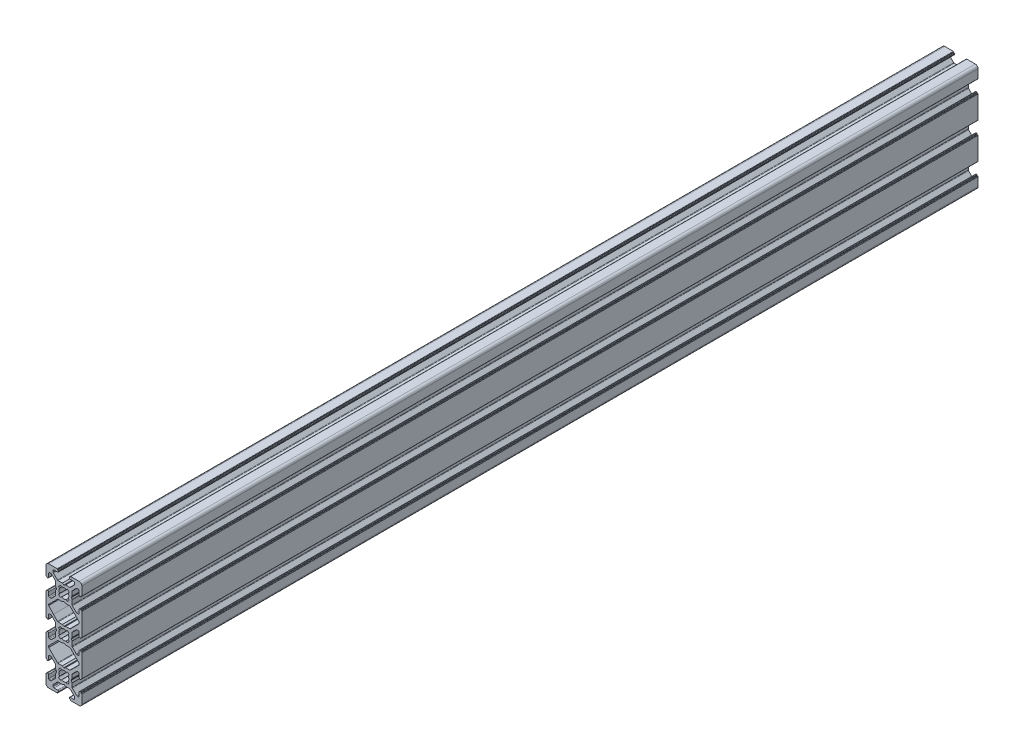
SolidWorks part; units mm, degrees
material "6061 Alloy"
ref_plane "Front Plane" through (0, 0, 0) normal (0, 0, 1) x (1, 0, 0)
ref_plane "Top Plane" through (0, 0, 0) normal (0, 1, 0) x (1, 0, 0)
ref_plane "Right Plane" through (0, 0, 0) normal (1, 0, 0) x (0, 0, -1)
sketch "Sketch2" plane through (0, 0, 0) normal (0, 0, 1) x (1, 0, 0)
  line L0 (0, -19.2121) -> (0, 56.5718) construction
  line L1 (8.5, 16.4558) -> (8.5, 14.5058)
  line L2 (10, 36.2558) -> (10, 23.6558)
  line L3 (-8.5, 30.4451) -> (-8.5, 29.884)
  line L4 (8.5, 30.4451) -> (8.5, 29.5607)
  line L5 (-3.5858, 4.6464) -> (-8.5, 9.5607)
  line L6 (-4.7214, 3.4608) -> (-7.1142, 5.8536)
  line L7 (-3.75, -10) -> (-8.5, -10)
  line L8 (-4.7214, -3.4608) -> (-7.1142, -5.8536)
  line L9 (-9.7, -3.55) -> (-9.8, -3.55)
  line L10 (-9.5, -3.2) -> (-9.5, -3.35)
  line L11 (-7.4678, -6) -> (-8, -6)
  line L12 (-9, -3) -> (-9.3, -3)
  line L13 (-8.5, -3.5) -> (-8.5, -5.5)
  line L14 (-10, -3.75) -> (-10, -8.5)
  line L15 (-7.4678, 6) -> (-8, 6)
  line L16 (-9.7, 3.55) -> (-9.8, 3.55)
  line L17 (-9.5, 3.2) -> (-9.5, 3.35)
  line L18 (-9, 3) -> (-9.3, 3)
  line L19 (-8.5, 3.5) -> (-8.5, 5.5)
  line L20 (-10, 16.2558) -> (-10, 3.75)
  line L21 (-4.575, -3.1072) -> (-4.575, -1.0835)
  line L22 (4.575, -3.1072) -> (4.575, -1.0835)
  line L23 (3.2322, -4.5) -> (0.9536, -4.5)
  line L24 (-3.2322, -4.5) -> (-0.9536, -4.5)
  line L25 (-0.8536, -4.4732) -> (-0.1, -4.0381)
  line L26 (0.8536, -4.4732) -> (0.1, -4.0381)
  line L27 (-3.5, -8.5) -> (-5.5, -8.5)
  line L28 (-3.2, -9.5) -> (-3.35, -9.5)
  line L29 (-3.55, -9.7) -> (-3.55, -9.8)
  line L30 (-6, -7.2678) -> (-6, -8)
  line L31 (-3.5858, -4.6464) -> (-5.8536, -6.9142)
  line L32 (-3, -9) -> (-3, -9.3)
  line L33 (3.55, -9.7) -> (3.55, -9.8)
  line L34 (3.2, -9.5) -> (3.35, -9.5)
  line L35 (6, -7.2678) -> (6, -8)
  line L36 (3, -9) -> (3, -9.3)
  line L37 (3.5, -8.5) -> (5.5, -8.5)
  line L38 (3.75, -10) -> (8.5, -10)
  line L39 (10, -3.7) -> (10, -8.5)
  line L40 (8.5, -3.5) -> (8.5, -5.5)
  line L41 (9.5, -3.2) -> (9.5, -3.3)
  line L42 (9.7, -3.5) -> (9.8, -3.5)
  line L43 (7.4678, -6) -> (8, -6)
  line L44 (4.7214, -3.4608) -> (7.1142, -5.8536)
  line L45 (3.5858, -4.6464) -> (5.8536, -6.9142)
  line L46 (9, -3) -> (9.3, -3)
  line L47 (3.5858, 4.6464) -> (8.5, 9.5607)
  line L48 (3.2322, 4.5) -> (0.9536, 4.5)
  line L49 (-3.2322, 4.5) -> (-0.9536, 4.5)
  line L50 (-0.8536, 4.4732) -> (-0.1, 4.0381)
  line L51 (0.8536, 4.4732) -> (0.1, 4.0381)
  line L52 (1.2582, 2.4453) -> (1.9099, 2.9922)
  line L53 (-4.575, 3.1072) -> (-4.575, 1.0835)
  line L54 (-4.5482, 0.9835) -> (-4.0381, 0.1)
  line L55 (-4.5482, -0.9835) -> (-4.0381, -0.1)
  line L56 (-1.2623, 2.4431) -> (-1.9139, 2.9896)
  line L57 (-2.4453, 1.2582) -> (-2.9922, 1.9099)
  line L58 (-2.4431, -1.2623) -> (-2.9897, -1.9139)
  line L59 (-1.2582, -2.4453) -> (-1.9099, -2.9922)
  line L60 (1.2623, -2.4431) -> (1.9139, -2.9897)
  line L61 (2.4453, 1.2582) -> (2.9896, 1.9139)
  line L62 (4.5482, -0.9835) -> (4.0381, -0.1)
  line L63 (4.5482, 0.9835) -> (4.0381, 0.1)
  line L64 (4.575, 3.1072) -> (4.575, 1.0835)
  line L65 (2.4453, -1.2582) -> (2.9922, -1.9099)
  line L66 (9.7, 3.5) -> (9.8, 3.5)
  line L67 (9.5, 3.2) -> (9.5, 3.3)
  line L68 (7.4678, 6) -> (8, 6)
  line L69 (9, 3) -> (9.3, 3)
  line L70 (8.5, 3.5) -> (8.5, 5.5)
  line L71 (10, 3.7) -> (10, 16.2558)
  line L72 (4.7214, 3.4608) -> (7.1142, 5.8536)
  line L73 (-4.7214, 36.345) -> (-6.9142, 34.1522)
  line L74 (-3.5858, 35.3593) -> (-8.5, 30.4451)
  line L75 (-4.7214, 43.6666) -> (-6.9142, 45.8593)
  line L76 (-3.75, 50) -> (-8.5, 50)
  line L77 (-10, 43.6558) -> (-10, 48.5)
  line L78 (-8.5, 43.4558) -> (-8.5, 45.5058)
  line L79 (0, 40.0058) -> (15.2221, 40.0058) construction
  line L80 (-8.5, 36.4558) -> (-8.5, 34.5058)
  line L81 (-9, 36.9558) -> (-9.3, 36.9558)
  line L82 (-7.2678, 34.0058) -> (-8, 34.0058)
  line L83 (-9.5, 36.7558) -> (-9.5, 36.6558)
  line L84 (-9.7, 36.4558) -> (-9.8, 36.4558)
  line L85 (-9, 42.9558) -> (-9.3, 42.9558)
  line L86 (-9.5, 43.1558) -> (-9.5, 43.2558)
  line L87 (-9.7, 43.4558) -> (-9.8, 43.4558)
  line L88 (-7.2678, 46.0058) -> (-8, 46.0058)
  line L89 (4.7214, 43.6666) -> (6.9142, 45.8593)
  line L90 (10, 43.6558) -> (10, 48.5)
  line L91 (8.5, 43.4558) -> (8.5, 45.5058)
  line L92 (3.5858, 35.3593) -> (8.5, 30.4451)
  line L93 (-4.7214, 16.345) -> (-6.9142, 14.1522)
  line L94 (3.2322, 35.5058) -> (0.9536, 35.5058)
  line L95 (1.2582, 37.5605) -> (1.8871, 37.0581)
  line L96 (-1.2582, 37.5605) -> (-1.8871, 37.0581)
  line L97 (-2.4453, 38.7476) -> (-2.9477, 38.1187)
  line L98 (-2.4453, 41.264) -> (-2.9477, 41.8928)
  line L99 (-1.2582, 42.4511) -> (-1.8871, 42.9535)
  line L100 (0.8536, 35.5326) -> (0.1, 35.9677)
  line L101 (-0.8536, 35.5326) -> (-0.1, 35.9677)
  line L102 (-3.2322, 35.5058) -> (-0.9536, 35.5058)
  line L103 (-4.575, 36.6986) -> (-4.575, 39.1772)
  line L104 (-4.5482, 39.2772) -> (-4.142, 39.9808)
  line L105 (-4.5482, 40.8844) -> (-4.142, 40.1808)
  line L106 (-4.575, 43.313) -> (-4.575, 40.9844)
  line L107 (1.2582, 42.4511) -> (1.8871, 42.9535)
  line L108 (9, 42.9558) -> (9.3, 42.9558)
  line L109 (9.5, 43.1558) -> (9.5, 43.2558)
  line L110 (9.7, 43.4558) -> (9.8, 43.4558)
  line L111 (9, 36.9558) -> (9.3, 36.9558)
  line L112 (4.7214, 36.345) -> (6.9142, 34.1522)
  line L113 (7.2678, 34.0058) -> (8, 34.0058)
  line L114 (9.7, 36.4558) -> (9.8, 36.4558)
  line L115 (9.5, 36.7558) -> (9.5, 36.6558)
  line L116 (8.5, 36.4558) -> (8.5, 34.5058)
  line L117 (2.4453, 38.7476) -> (2.9477, 38.1187)
  line L118 (4.575, 43.313) -> (4.575, 40.9844)
  line L119 (4.5482, 40.8844) -> (4.142, 40.1808)
  line L120 (4.5482, 39.2772) -> (4.142, 39.9808)
  line L121 (4.575, 36.6986) -> (4.575, 39.1772)
  line L122 (2.4453, 41.264) -> (2.9477, 41.8928)
  line L123 (3.2322, 44.5) -> (0.9536, 44.5)
  line L124 (-3.55, 49.7) -> (-3.55, 49.8)
  line L125 (-3.2, 49.5) -> (-3.35, 49.5)
  line L126 (-3.5858, 44.6464) -> (-5.8536, 46.9142)
  line L127 (-6, 47.2678) -> (-6, 48)
  line L128 (0.8536, 44.4732) -> (0.0592, 44.0146)
  line L129 (-0.8536, 44.4732) -> (-0.0592, 44.0146)
  line L130 (-3.2322, 44.5) -> (-0.9536, 44.5)
  line L131 (-3, 49) -> (-3, 49.3)
  line L132 (-3.5, 48.5) -> (-5.5, 48.5)
  line L133 (3, 49) -> (3, 49.3)
  line L134 (3.5858, 44.6464) -> (5.8536, 46.9142)
  line L135 (6, 47.2678) -> (6, 48)
  line L136 (3.55, 49.7) -> (3.55, 49.8)
  line L137 (3.2, 49.5) -> (3.35, 49.5)
  line L138 (3.5, 48.5) -> (5.5, 48.5)
  line L139 (3.75, 50) -> (8.5, 50)
  line L140 (-34.2612, 0) -> (36.5039, 0) construction
  line L141 (-3.5858, 15.3593) -> (-8.5, 10.4451)
  line L142 (-4.7214, 23.6666) -> (-6.9142, 25.8593)
  line L143 (-8.5, 10.4451) -> (-8.5, 9.5607)
  line L144 (-9.5, 16.7558) -> (-9.5, 16.6558)
  line L145 (-9.7, 16.4558) -> (-9.8, 16.4558)
  line L146 (-9, 16.9558) -> (-9.3, 16.9558)
  line L147 (-7.2678, 14.0058) -> (-8, 14.0058)
  line L148 (-5.8536, 26.9142) -> (-8.5, 29.884)
  line L149 (-8.5, 16.4558) -> (-8.5, 14.5058)
  line L150 (-9.8, 23.4558) -> (-9.7, 23.4558)
  line L151 (-9, 22.9558) -> (-9.3, 22.9558)
  line L152 (-9.5, 23.1558) -> (-9.5, 23.2558)
  line L153 (-7.2678, 26.0058) -> (-8, 26.0058)
  line L154 (7.2678, 26.0058) -> (8, 26.0058)
  line L155 (4.7214, 23.6666) -> (6.9142, 25.8593)
  line L156 (-10, 36.2558) -> (-10, 23.6558)
  line L157 (8.5, 25.5058) -> (8.5, 23.4558)
  line L158 (3.5858, 15.3593) -> (8.5, 10.4451)
  line L159 (3.2322, 15.5058) -> (0.9536, 15.5058)
  line L160 (1.2582, 17.5605) -> (1.8871, 17.0581)
  line L161 (-1.2582, 17.5605) -> (-1.8871, 17.0581)
  line L162 (-2.4453, 18.7476) -> (-2.9477, 18.1187)
  line L163 (-2.4453, 21.264) -> (-2.9477, 21.8928)
  line L164 (-1.2582, 22.4511) -> (-1.8871, 22.9535)
  line L165 (0.8536, 15.5326) -> (0.1, 15.9677)
  line L166 (-0.8536, 15.5326) -> (-0.1, 15.9677)
  line L167 (-3.2322, 15.5058) -> (-0.9536, 15.5058)
  line L168 (-4.575, 16.6986) -> (-4.575, 19.1772)
  line L169 (-4.5482, 19.2772) -> (-4.142, 19.9808)
  line L170 (-4.5482, 20.8844) -> (-4.142, 20.1808)
  line L171 (-4.575, 23.313) -> (-4.575, 20.9844)
  line L172 (1.2582, 22.4511) -> (1.8871, 22.9535)
  line L173 (9, 22.9558) -> (9.3, 22.9558)
  line L174 (9.5, 23.1558) -> (9.5, 23.2558)
  line L175 (9.8, 23.4558) -> (9.7, 23.4558)
  line L176 (9, 16.9558) -> (9.3, 16.9558)
  line L177 (4.7214, 16.345) -> (6.9142, 14.1522)
  line L178 (7.2678, 14.0058) -> (8, 14.0058)
  line L179 (9.7, 16.4558) -> (9.8, 16.4558)
  line L180 (9.5, 16.7558) -> (9.5, 16.6558)
  line L181 (5.8536, 26.9142) -> (8.5, 29.5607)
  line L182 (2.4453, 18.7476) -> (2.9477, 18.1187)
  line L183 (4.575, 23.313) -> (4.575, 20.9844)
  line L184 (4.5482, 20.8844) -> (4.142, 20.1808)
  line L185 (4.5482, 19.2772) -> (4.142, 19.9808)
  line L186 (4.575, 16.6986) -> (4.575, 19.1772)
  line L187 (2.4453, 21.264) -> (2.9477, 21.8928)
  line L188 (3.2322, 24.5) -> (0.9536, 24.5)
  line L191 (-3.5858, 24.6464) -> (-5.8536, 26.9142)
  line L192 (-8.5, 25.5058) -> (-8.5, 23.4558)
  line L193 (0.8536, 24.4732) -> (0.0592, 24.0146)
  line L194 (-0.8536, 24.4732) -> (-0.0592, 24.0146)
  line L195 (-3.2322, 24.5) -> (-0.9536, 24.5)
  line L196 (8.5, 10.4451) -> (8.5, 9.5607)
  line L199 (3.5858, 24.6464) -> (5.8536, 26.9142)
  line L206 (0, 20.0058) -> (15.2221, 20.0058) construction
  line L279 (7.2678, 46.0058) -> (8, 46.0058)
  line L280 (-3.75, 30) -> (-8.5, 30) [skipped]
  line L281 (-3.55, 29.7) -> (-3.55, 29.8) [skipped]
  line L282 (-3.2, 29.5) -> (-3.35, 29.5) [skipped]
  line L283 (-3, 29) -> (-3, 29.3) [skipped]
  line L284 (-3.5, 28.5) -> (-5.5, 28.5) [skipped]
  line L285 (-6, 27.2678) -> (-6, 28) [skipped]
  line L286 (3.5, 28.5) -> (5.5, 28.5) [skipped]
  line L287 (3, 29) -> (3, 29.3) [skipped]
  line L288 (3.75, 30) -> (8.5, 30) [skipped]
  line L289 (3.55, 29.7) -> (3.55, 29.8) [skipped]
  line L290 (3.2, 29.5) -> (3.35, 29.5) [skipped]
  line L291 (6, 27.2678) -> (6, 28) [skipped]
  line L292 (10, 23.6558) -> (10, 28.5) [skipped]
  line L293 (8.5, 16.4558) -> (8.5, 14.5058) [skipped]
  line L294 (-7.2678, 14.0058) -> (-8, 14.0058) [skipped]
  line L295 (-10, 23.6558) -> (-10, 28.5) [skipped]
  line L296 (-9.7, 23.4558) -> (-9.8, 23.4558) [skipped]
  line L297 (-7.2678, 26.0058) -> (-8, 26.0058) [skipped]
  line L298 (-8.5, 23.4558) -> (-8.5, 25.5058) [skipped]
  line L299 (-8.5, 16.4558) -> (-8.5, 14.5058) [skipped]
  line L300 (-9, 16.9558) -> (-9.3, 16.9558) [skipped]
  line L301 (-9.5, 16.7558) -> (-9.5, 16.6558) [skipped]
  line L302 (-9.7, 16.4558) -> (-9.8, 16.4558) [skipped]
  line L303 (9, 22.9558) -> (9.3, 22.9558) [skipped]
  line L304 (9.5, 23.1558) -> (9.5, 23.2558) [skipped]
  line L305 (9.7, 23.4558) -> (9.8, 23.4558) [skipped]
  line L306 (7.2678, 26.0058) -> (8, 26.0058) [skipped]
  line L307 (8.5, 23.4558) -> (8.5, 25.5058) [skipped]
  arc A0 (-5.8536, -6.9142) -> (-6, -7.2678) centre (-5.5, -7.2678) ccw
  arc A1 (-6, -8) -> (-5.5, -8.5) centre (-5.5, -8) ccw
  arc A2 (-8.5, -3.5) -> (-9, -3) centre (-9, -3.5) ccw
  arc A3 (-9.7, -3.55) -> (-9.5, -3.35) centre (-9.7, -3.35) ccw
  arc A4 (-9.8, -3.55) -> (-10, -3.75) centre (-9.8, -3.75) ccw
  arc A5 (-9.3, -3) -> (-9.5, -3.2) centre (-9.3, -3.2) ccw
  arc A6 (-7.4678, -6) -> (-7.1142, -5.8536) centre (-7.4678, -5.5) ccw
  arc A7 (-10, -8.5) -> (-8.5, -10) centre (-8.5, -8.5) ccw
  arc A8 (-8.5, -5.5) -> (-8, -6) centre (-8, -5.5) ccw
  arc A9 (-8, 6) -> (-8.5, 5.5) centre (-8, 5.5) ccw
  arc A10 (-7.1142, 5.8536) -> (-7.4678, 6) centre (-7.4678, 5.5) ccw
  arc A11 (-9.5, 3.35) -> (-9.7, 3.55) centre (-9.7, 3.35) ccw
  arc A12 (-10, 3.75) -> (-9.8, 3.55) centre (-9.8, 3.75) ccw
  arc A13 (-9.5, 3.2) -> (-9.3, 3) centre (-9.3, 3.2) ccw
  arc A14 (-9, 3) -> (-8.5, 3.5) centre (-9, 3.5) ccw
  arc A15 (9, -3) -> (8.5, -3.5) centre (9, -3.5) ccw
  arc A16 (-4.7214, -3.4608) -> (-4.575, -3.1072) centre (-5.075, -3.1072) ccw
  arc A17 (-3.2322, -4.5) -> (-3.5858, -4.6464) centre (-3.2322, -5) ccw
  arc A18 (0.8536, -4.4732) -> (0.9536, -4.5) centre (0.9536, -4.3) ccw
  arc A19 (-0.9536, -4.5) -> (-0.8536, -4.4732) centre (-0.9536, -4.3) ccw
  arc A20 (0.1, -4.0381) -> (-0.1, -4.0381) centre (0, -4.2113) ccw
  arc A21 (-3.2, -9.5) -> (-3, -9.3) centre (-3.2, -9.3) ccw
  arc A22 (-3.75, -10) -> (-3.55, -9.8) centre (-3.75, -9.8) ccw
  arc A23 (-3.35, -9.5) -> (-3.55, -9.7) centre (-3.35, -9.7) ccw
  arc A24 (-3, -9) -> (-3.5, -8.5) centre (-3.5, -9) ccw
  arc A25 (3.5858, -4.6464) -> (3.2322, -4.5) centre (3.2322, -5) ccw
  arc A26 (4.575, -3.1072) -> (4.7214, -3.4608) centre (5.075, -3.1072) ccw
  arc A27 (3.55, -9.7) -> (3.35, -9.5) centre (3.35, -9.7) ccw
  arc A28 (3.55, -9.8) -> (3.75, -10) centre (3.75, -9.8) ccw
  arc A29 (3, -9.3) -> (3.2, -9.5) centre (3.2, -9.3) ccw
  arc A30 (6, -7.2678) -> (5.8536, -6.9142) centre (5.5, -7.2678) ccw
  arc A31 (8.5, -10) -> (10, -8.5) centre (8.5, -8.5) ccw
  arc A32 (5.5, -8.5) -> (6, -8) centre (5.5, -8) ccw
  arc A33 (9.5, -3.2) -> (9.3, -3) centre (9.3, -3.2) ccw
  arc A34 (10, -3.7) -> (9.8, -3.5) centre (9.8, -3.7) ccw
  arc A35 (9.5, -3.3) -> (9.7, -3.5) centre (9.7, -3.3) ccw
  arc A36 (7.1142, -5.8536) -> (7.4678, -6) centre (7.4678, -5.5) ccw
  arc A37 (8, -6) -> (8.5, -5.5) centre (8, -5.5) ccw
  arc A38 (3.5, -8.5) -> (3, -9) centre (3.5, -9) ccw
  arc A39 (2.9896, 1.9139) -> (1.9099, 2.9922) centre (0, 0) ccw
  arc A40 (1.9139, -2.9897) -> (2.9922, -1.9099) centre (0, 0) ccw
  arc A41 (1.2582, 2.4453) -> (-1.2623, 2.4431) centre (0, 0) ccw
  arc A42 (-0.1, 4.0381) -> (0.1, 4.0381) centre (0, 4.2113) ccw
  arc A43 (0.9536, 4.5) -> (0.8536, 4.4732) centre (0.9536, 4.3) ccw
  arc A44 (-0.8536, 4.4732) -> (-0.9536, 4.5) centre (-0.9536, 4.3) ccw
  arc A45 (-3.5858, 4.6464) -> (-3.2322, 4.5) centre (-3.2322, 5) ccw
  arc A46 (-4.575, 3.1072) -> (-4.7214, 3.4608) centre (-5.075, 3.1072) ccw
  arc A47 (-4.5482, -0.9835) -> (-4.575, -1.0835) centre (-4.375, -1.0835) ccw
  arc A48 (-4.575, 1.0835) -> (-4.5482, 0.9835) centre (-4.375, 1.0835) ccw
  arc A49 (-4.0381, -0.1) -> (-4.0381, 0.1) centre (-4.2113, 0) ccw
  arc A50 (-1.9139, 2.9896) -> (-2.9922, 1.9099) centre (0, 0) ccw
  arc A51 (-2.9897, -1.9139) -> (-1.9099, -2.9922) centre (0, 0) ccw
  arc A52 (-2.4453, 1.2582) -> (-2.4431, -1.2623) centre (0, 0) ccw
  arc A53 (-1.2582, -2.4453) -> (1.2623, -2.4431) centre (0, 0) ccw
  arc A54 (3.2322, 4.5) -> (3.5858, 4.6464) centre (3.2322, 5) ccw
  arc A55 (4.7214, 3.4608) -> (4.575, 3.1072) centre (5.075, 3.1072) ccw
  arc A56 (4.5482, 0.9835) -> (4.575, 1.0835) centre (4.375, 1.0835) ccw
  arc A57 (4.575, -1.0835) -> (4.5482, -0.9835) centre (4.375, -1.0835) ccw
  arc A58 (4.0381, 0.1) -> (4.0381, -0.1) centre (4.2113, 0) ccw
  arc A59 (2.4453, -1.2582) -> (2.4453, 1.2582) centre (0, 0) ccw
  arc A60 (9.7, 3.5) -> (9.5, 3.3) centre (9.7, 3.3) ccw
  arc A61 (9.8, 3.5) -> (10, 3.7) centre (9.8, 3.7) ccw
  arc A62 (9.3, 3) -> (9.5, 3.2) centre (9.3, 3.2) ccw
  arc A63 (7.4678, 6) -> (7.1142, 5.8536) centre (7.4678, 5.5) ccw
  arc A64 (8.5, 5.5) -> (8, 6) centre (8, 5.5) ccw
  arc A65 (8.5, 3.5) -> (9, 3) centre (9, 3.5) ccw
  arc A66 (-6, 47.2678) -> (-5.8536, 46.9142) centre (-5.5, 47.2678) ccw
  arc A67 (-5.5, 48.5) -> (-6, 48) centre (-5.5, 48) ccw
  arc A68 (-9, 42.9558) -> (-8.5, 43.4558) centre (-9, 43.4558) ccw
  arc A69 (-8.5, 36.4558) -> (-9, 36.9558) centre (-9, 36.4558) ccw
  arc A70 (-8.5, 34.5058) -> (-8, 34.0058) centre (-8, 34.5058) ccw
  arc A71 (-7.2678, 34.0058) -> (-6.9142, 34.1522) centre (-7.2678, 34.5058) ccw
  arc A72 (-9.3, 36.9558) -> (-9.5, 36.7558) centre (-9.3, 36.7558) ccw
  arc A73 (-9.8, 36.4558) -> (-10, 36.2558) centre (-9.8, 36.2558) ccw
  arc A74 (-9.7, 36.4558) -> (-9.5, 36.6558) centre (-9.7, 36.6558) ccw
  arc A75 (-9.5, 43.1558) -> (-9.3, 42.9558) centre (-9.3, 43.1558) ccw
  arc A76 (-10, 43.6558) -> (-9.8, 43.4558) centre (-9.8, 43.6558) ccw
  arc A77 (-9.5, 43.2558) -> (-9.7, 43.4558) centre (-9.7, 43.2558) ccw
  arc A78 (-6.9142, 45.8593) -> (-7.2678, 46.0058) centre (-7.2678, 45.5058) ccw
  arc A79 (-8, 46.0058) -> (-8.5, 45.5058) centre (-8, 45.5058) ccw
  arc A80 (-8.5, 50) -> (-10, 48.5) centre (-8.5, 48.5) ccw
  arc A81 (1.8871, 37.0581) -> (2.9477, 38.1187) centre (0, 40.0058) ccw
  arc A82 (2.9477, 41.8928) -> (1.8871, 42.9535) centre (0, 40.0058) ccw
  arc A83 (-1.2582, 37.5605) -> (1.2582, 37.5605) centre (0, 40.0058) ccw
  arc A84 (-2.4453, 41.264) -> (-2.4453, 38.7476) centre (0, 40.0058) ccw
  arc A85 (-2.9477, 38.1187) -> (-1.8871, 37.0581) centre (0, 40.0058) ccw
  arc A86 (-1.8871, 42.9535) -> (-2.9477, 41.8928) centre (0, 40.0058) ccw
  arc A87 (0.1, 35.9677) -> (-0.1, 35.9677) centre (0, 35.7945) ccw
  arc A88 (-0.9536, 35.5058) -> (-0.8536, 35.5326) centre (-0.9536, 35.7058) ccw
  arc A89 (0.8536, 35.5326) -> (0.9536, 35.5058) centre (0.9536, 35.7058) ccw
  arc A90 (-3.2322, 35.5058) -> (-3.5858, 35.3593) centre (-3.2322, 35.0058) ccw
  arc A91 (-4.142, 39.9808) -> (-4.142, 40.1808) centre (-4.3152, 40.0808) ccw
  arc A92 (-4.575, 40.9844) -> (-4.5482, 40.8844) centre (-4.375, 40.9844) ccw
  arc A93 (-4.5482, 39.2772) -> (-4.575, 39.1772) centre (-4.375, 39.1772) ccw
  arc A94 (-4.575, 43.313) -> (-4.7214, 43.6666) centre (-5.075, 43.313) ccw
  arc A95 (-4.7214, 36.345) -> (-4.575, 36.6986) centre (-5.075, 36.6986) ccw
  arc A96 (1.2582, 42.4511) -> (-1.2582, 42.4511) centre (0, 40.0058) ccw
  arc A97 (9, 36.9558) -> (8.5, 36.4558) centre (9, 36.4558) ccw
  arc A98 (8.5, 43.4558) -> (9, 42.9558) centre (9, 43.4558) ccw
  arc A99 (9.3, 42.9558) -> (9.5, 43.1558) centre (9.3, 43.1558) ccw
  arc A100 (9.8, 43.4558) -> (10, 43.6558) centre (9.8, 43.6558) ccw
  arc A101 (9.7, 43.4558) -> (9.5, 43.2558) centre (9.7, 43.2558) ccw
  arc A102 (8, 34.0058) -> (8.5, 34.5058) centre (8, 34.5058) ccw
  arc A103 (6.9142, 34.1522) -> (7.2678, 34.0058) centre (7.2678, 34.5058) ccw
  arc A104 (9.5, 36.6558) -> (9.7, 36.4558) centre (9.7, 36.6558) ccw
  arc A105 (10, 36.2558) -> (9.8, 36.4558) centre (9.8, 36.2558) ccw
  arc A106 (9.5, 36.7558) -> (9.3, 36.9558) centre (9.3, 36.7558) ccw
  arc A107 (2.4453, 38.7476) -> (2.4453, 41.264) centre (0, 40.0058) ccw
  arc A108 (4.142, 40.1808) -> (4.142, 39.9808) centre (4.3152, 40.0808) ccw
  arc A109 (4.575, 39.1772) -> (4.5482, 39.2772) centre (4.375, 39.1772) ccw
  arc A110 (4.5482, 40.8844) -> (4.575, 40.9844) centre (4.375, 40.9844) ccw
  arc A111 (4.575, 36.6986) -> (4.7214, 36.345) centre (5.075, 36.6986) ccw
  arc A112 (4.7214, 43.6666) -> (4.575, 43.313) centre (5.075, 43.313) ccw
  arc A113 (3.5858, 35.3593) -> (3.2322, 35.5058) centre (3.2322, 35.0058) ccw
  arc A114 (-3.5, 48.5) -> (-3, 49) centre (-3.5, 49) ccw
  arc A115 (-3.55, 49.7) -> (-3.35, 49.5) centre (-3.35, 49.7) ccw
  arc A116 (-3.55, 49.8) -> (-3.75, 50) centre (-3.75, 49.8) ccw
  arc A117 (-3, 49.3) -> (-3.2, 49.5) centre (-3.2, 49.3) ccw
  arc A118 (-3.5858, 44.6464) -> (-3.2322, 44.5) centre (-3.2322, 45) ccw
  arc A119 (-0.8536, 44.4732) -> (-0.9536, 44.5) centre (-0.9536, 44.3) ccw
  arc A120 (0.9536, 44.5) -> (0.8536, 44.4732) centre (0.9536, 44.3) ccw
  arc A121 (-0.0592, 44.0146) -> (0.0592, 44.0146) centre (0, 44.1171) ccw
  arc A122 (3, 49) -> (3.5, 48.5) centre (3.5, 49) ccw
  arc A123 (6, 48) -> (5.5, 48.5) centre (5.5, 48) ccw
  arc A124 (5.8536, 46.9142) -> (6, 47.2678) centre (5.5, 47.2678) ccw
  arc A125 (3.35, 49.5) -> (3.55, 49.7) centre (3.35, 49.7) ccw
  arc A126 (3.75, 50) -> (3.55, 49.8) centre (3.75, 49.8) ccw
  arc A127 (3.2, 49.5) -> (3, 49.3) centre (3.2, 49.3) ccw
  arc A128 (8.5, 45.5058) -> (8, 46.0058) centre (8, 45.5058) ccw
  arc A129 (10, 48.5) -> (8.5, 50) centre (8.5, 48.5) ccw
  arc A130 (7.2678, 46.0058) -> (6.9142, 45.8593) centre (7.2678, 45.5058) ccw
  arc A131 (3.2322, 44.5) -> (3.5858, 44.6464) centre (3.2322, 45) ccw
  arc A132 (-7.2678, 26.0058) -> (-6.9142, 25.8593) centre (-7.2678, 25.5058) cw
  arc A133 (-9.5, 16.7558) -> (-9.3, 16.9558) centre (-9.3, 16.7558) cw
  arc A134 (-9, 22.9558) -> (-8.5, 23.4558) centre (-9, 23.4558) ccw
  arc A135 (-10, 16.2558) -> (-9.8, 16.4558) centre (-9.8, 16.2558) cw
  arc A136 (-9.5, 16.6558) -> (-9.7, 16.4558) centre (-9.7, 16.6558) cw
  arc A137 (-7.2678, 14.0058) -> (-6.9142, 14.1522) centre (-7.2678, 14.5058) ccw
  arc A138 (-9, 16.9558) -> (-8.5, 16.4558) centre (-9, 16.4558) cw
  arc A139 (-8, 14.0058) -> (-8.5, 14.5058) centre (-8, 14.5058) cw
  arc A140 (8, 26.0058) -> (8.5, 25.5058) centre (8, 25.5058) cw
  arc A141 (-9.5, 23.1558) -> (-9.3, 22.9558) centre (-9.3, 23.1558) ccw
  arc A142 (-10, 23.6558) -> (-9.8, 23.4558) centre (-9.8, 23.6558) ccw
  arc A143 (-9.5, 23.2558) -> (-9.7, 23.4558) centre (-9.7, 23.2558) ccw
  arc A144 (9, 22.9558) -> (8.5, 23.4558) centre (9, 23.4558) cw
  arc A145 (-8, 26.0058) -> (-8.5, 25.5058) centre (-8, 25.5058) ccw
  arc A146 (9.5, 23.1558) -> (9.3, 22.9558) centre (9.3, 23.1558) cw
  arc A147 (1.8871, 17.0581) -> (2.9477, 18.1187) centre (0, 20.0058) ccw
  arc A148 (2.9477, 21.8928) -> (1.8871, 22.9535) centre (0, 20.0058) ccw
  arc A149 (-1.2582, 17.5605) -> (1.2582, 17.5605) centre (0, 20.0058) ccw
  arc A150 (-2.4453, 21.264) -> (-2.4453, 18.7476) centre (0, 20.0058) ccw
  arc A151 (-2.9477, 18.1187) -> (-1.8871, 17.0581) centre (0, 20.0058) ccw
  arc A152 (-1.8871, 22.9535) -> (-2.9477, 21.8928) centre (0, 20.0058) ccw
  arc A153 (0.1, 15.9677) -> (-0.1, 15.9677) centre (0, 15.7945) ccw
  arc A154 (-0.9536, 15.5058) -> (-0.8536, 15.5326) centre (-0.9536, 15.7058) ccw
  arc A155 (0.8536, 15.5326) -> (0.9536, 15.5058) centre (0.9536, 15.7058) ccw
  arc A156 (-3.2322, 15.5058) -> (-3.5858, 15.3593) centre (-3.2322, 15.0058) ccw
  arc A157 (-4.142, 19.9808) -> (-4.142, 20.1808) centre (-4.3152, 20.0808) ccw
  arc A158 (-4.575, 20.9844) -> (-4.5482, 20.8844) centre (-4.375, 20.9844) ccw
  arc A159 (-4.5482, 19.2772) -> (-4.575, 19.1772) centre (-4.375, 19.1772) ccw
  arc A160 (-4.575, 23.313) -> (-4.7214, 23.6666) centre (-5.075, 23.313) ccw
  arc A161 (-4.7214, 16.345) -> (-4.575, 16.6986) centre (-5.075, 16.6986) ccw
  arc A162 (1.2582, 22.4511) -> (-1.2582, 22.4511) centre (0, 20.0058) ccw
  arc A163 (9, 16.9558) -> (8.5, 16.4558) centre (9, 16.4558) ccw
  arc A164 (9.5, 23.2558) -> (9.7, 23.4558) centre (9.7, 23.2558) cw
  arc A165 (10, 23.6558) -> (9.8, 23.4558) centre (9.8, 23.6558) cw
  arc A168 (8, 14.0058) -> (8.5, 14.5058) centre (8, 14.5058) ccw
  arc A169 (6.9142, 14.1522) -> (7.2678, 14.0058) centre (7.2678, 14.5058) ccw
  arc A170 (9.5, 16.6558) -> (9.7, 16.4558) centre (9.7, 16.6558) ccw
  arc A171 (10, 16.2558) -> (9.8, 16.4558) centre (9.8, 16.2558) ccw
  arc A172 (9.5, 16.7558) -> (9.3, 16.9558) centre (9.3, 16.7558) ccw
  arc A173 (2.4453, 18.7476) -> (2.4453, 21.264) centre (0, 20.0058) ccw
  arc A174 (4.142, 20.1808) -> (4.142, 19.9808) centre (4.3152, 20.0808) ccw
  arc A175 (4.575, 19.1772) -> (4.5482, 19.2772) centre (4.375, 19.1772) ccw
  arc A176 (4.5482, 20.8844) -> (4.575, 20.9844) centre (4.375, 20.9844) ccw
  arc A177 (4.575, 16.6986) -> (4.7214, 16.345) centre (5.075, 16.6986) ccw
  arc A178 (4.7214, 23.6666) -> (4.575, 23.313) centre (5.075, 23.313) ccw
  arc A179 (3.5858, 15.3593) -> (3.2322, 15.5058) centre (3.2322, 15.0058) ccw
  arc A184 (-3.5858, 24.6464) -> (-3.2322, 24.5) centre (-3.2322, 25) ccw
  arc A185 (-0.8536, 24.4732) -> (-0.9536, 24.5) centre (-0.9536, 24.3) ccw
  arc A186 (0.9536, 24.5) -> (0.8536, 24.4732) centre (0.9536, 24.3) ccw
  arc A187 (-0.0592, 24.0146) -> (0.0592, 24.0146) centre (0, 24.1171) ccw
  arc A196 (7.2678, 26.0058) -> (6.9142, 25.8593) centre (7.2678, 25.5058) ccw
  arc A197 (3.2322, 24.5) -> (3.5858, 24.6464) centre (3.2322, 25) ccw
  arc A198 (-8.5, 30) -> (-10, 28.5) centre (-8.5, 28.5) ccw [skipped]
  arc A199 (-3, 29.3) -> (-3.2, 29.5) centre (-3.2, 29.3) ccw [skipped]
  arc A200 (-3.5, 28.5) -> (-3, 29) centre (-3.5, 29) ccw [skipped]
  arc A201 (-3.55, 29.7) -> (-3.35, 29.5) centre (-3.35, 29.7) ccw [skipped]
  arc A202 (-3.55, 29.8) -> (-3.75, 30) centre (-3.75, 29.8) ccw [skipped]
  arc A203 (-5.5, 28.5) -> (-6, 28) centre (-5.5, 28) ccw [skipped]
  arc A204 (-6, 27.2678) -> (-5.8536, 26.9142) centre (-5.5, 27.2678) ccw [skipped]
  arc A205 (3, 29) -> (3.5, 28.5) centre (3.5, 29) ccw [skipped]
  arc A206 (3.35, 29.5) -> (3.55, 29.7) centre (3.35, 29.7) ccw [skipped]
  arc A207 (3.2, 29.5) -> (3, 29.3) centre (3.2, 29.3) ccw [skipped]
  arc A208 (3.75, 30) -> (3.55, 29.8) centre (3.75, 29.8) ccw [skipped]
  arc A209 (6, 28) -> (5.5, 28.5) centre (5.5, 28) ccw [skipped]
  arc A210 (5.8536, 26.9142) -> (6, 27.2678) centre (5.5, 27.2678) ccw [skipped]
  arc A211 (10, 28.5) -> (8.5, 30) centre (8.5, 28.5) ccw [skipped]
  arc A212 (-6.9142, 25.8593) -> (-7.2678, 26.0058) centre (-7.2678, 25.5058) ccw [skipped]
  arc A213 (-8.5, 16.4558) -> (-9, 16.9558) centre (-9, 16.4558) ccw [skipped]
  arc A214 (-8.5, 14.5058) -> (-8, 14.0058) centre (-8, 14.5058) ccw [skipped]
  arc A215 (-9.3, 16.9558) -> (-9.5, 16.7558) centre (-9.3, 16.7558) ccw [skipped]
  arc A216 (-9.8, 16.4558) -> (-10, 16.2558) centre (-9.8, 16.2558) ccw [skipped]
  arc A217 (-9.7, 16.4558) -> (-9.5, 16.6558) centre (-9.7, 16.6558) ccw [skipped]
  arc A218 (8.5, 23.4558) -> (9, 22.9558) centre (9, 23.4558) ccw [skipped]
  arc A219 (9.3, 22.9558) -> (9.5, 23.1558) centre (9.3, 23.1558) ccw [skipped]
  arc A220 (9.8, 23.4558) -> (10, 23.6558) centre (9.8, 23.6558) ccw [skipped]
  arc A221 (9.7, 23.4558) -> (9.5, 23.2558) centre (9.7, 23.2558) ccw [skipped]
  arc A222 (8.5, 25.5058) -> (8, 26.0058) centre (8, 25.5058) ccw [skipped]
  dimension "D3" = 5.5
  dimension "D6" = 5.5
  dimension "D1" = 60
  dimension "D2" = 20
  dimension "D4" = 6
  dimension "D5" = 6
  dimension "D7" = 12
  dimension "D8" = 12
  dimension "D9" = 12
  dimension "D10" = 12
  dimension "D11" = 12
  dimension "D12" = 12
  dimension "D13" = 2
extrude "Extrude1" add sketch "Sketch2" along normal blind 500
sketch "Sketch3" plane through (-10, 0, 0) normal (-1, 0, 0) x (0, 0, 1)
  line L0 (500, 40.0808) -> (0, 40.0808) construction
  line L2 (500, 39.9808) -> (500, 40.1808) construction
  line L3 (0, 40.1808) -> (0, 39.9808) construction
